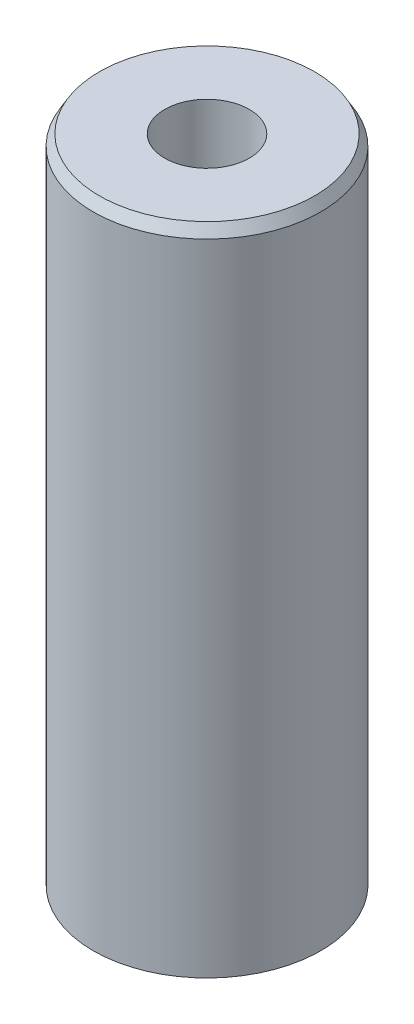
SolidWorks part; units mm, degrees
ref_plane "Front Plane" through (0, 0, 0) normal (0, 0, 1) x (1, 0, 0)
ref_plane "Top Plane" through (0, 0, 0) normal (0, 1, 0) x (1, 0, 0)
ref_plane "Right Plane" through (0, 0, 0) normal (1, 0, 0) x (0, 0, -1)
sketch "Sketch1" plane through (0, 0, 0) normal (0, 1, 0) x (1, 0, 0)
  circle A0 centre (0, 0) radius 35
  dimension "SHAFT_OD" = 70
extrude "Boss-Extrude1" add sketch "Sketch1" along normal blind 202.0166
sketch "Sketch2" plane through (0, 0, 0) normal (0, 1, 0) x (1, 0, 0)
  circle A0 centre (0, 0) radius 13.0093
  dimension "BORE_D" = 26.0186
extrude "Cut-Extrude1" cut sketch "Sketch2" along normal through all
chamfer "Chamfer1" distance 3.3114 angle 30 2 edges at (0, 202.0166, 35) (0, 0, 35) first distance on face at (0, 202.0166, 35) first distance on face at (0, 0, 13.0093)
